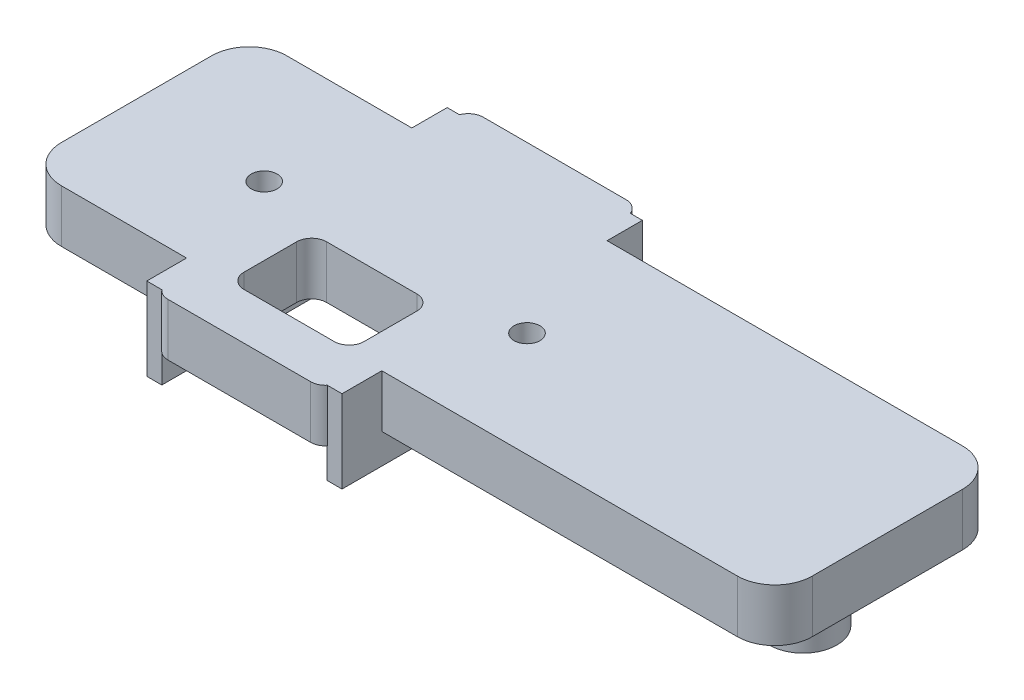
SolidWorks part; units mm, degrees
ref_plane "Front Plane" through (0, 0, 0) normal (0, 0, 1) x (1, 0, 0)
ref_plane "Top Plane" through (0, 0, 0) normal (0, 1, 0) x (1, 0, 0)
ref_plane "Right Plane" through (0, 0, 0) normal (1, 0, 0) x (0, 0, -1)
sketch "Sketch1" plane through (0, 0, 0) normal (0, 1, 0) x (1, 0, 0)
  line L1 (-45.1945, 17.8802) -> (54.8055, 17.8802)
  line L2 (-45.1945, 17.8802) -> (-45.1945, -12.1198)
  line L3 (-45.1945, -12.1198) -> (54.8055, -12.1198)
  line L4 (54.8055, 17.8802) -> (54.8055, -12.1198)
  dimension "D1" = 100
  dimension "D2" = 30
extrude "Boss-Extrude1" add sketch "Sketch1" along normal blind 7
ref_plane "Plane1" through (0, -1, 0) normal (0, -1, 0) x (-1, 0, 0)
sketch "Sketch2" plane through (0, -1, 0) normal (0, -1, 0) x (-1, 0, 0)
  line L0 (-54.8055, 2.8802) -> (57.5711, 2.8802) construction
  line L1 (-41.1646, -0.0198) -> (-44.5646, -0.0198)
  line L2 (-41.1646, -0.0198) -> (-41.1646, 5.7802)
  line L3 (-41.1646, 5.7802) -> (-44.5646, 5.7802)
  line L4 (-44.5646, -0.0198) -> (-44.5646, 5.7802)
  line L5 (-54.8055, -12.1198) -> (-54.8055, 17.8802) construction
  line L6 (-42.8646, -12.1198) -> (-42.8646, 27.765) construction
  line L8 (45.1945, -12.1198) -> (-54.8055, -12.1198) construction
  dimension "D1" = 3.4
  dimension "D2" = 5.8
  dimension "D3" = 1.7
  dimension "D4" = 2.9
extrude "Boss-Extrude2" add sketch "Sketch2" along normal blind 6 separate body
shell "Shell1" thickness 1 removed face at (42.8646, -7, -2.8802) outward yes
sketch "Sketch3" plane through (0, 0, 0) normal (0, -1, 0) x (-1, 0, 0)
  line L0 (-42.8646, -0.0198) -> (-42.8646, 11.0227) construction
  line L1 (-44.5646, -0.0198) -> (-41.1646, -0.0198) construction
  line L2 (-41.1646, 2.8802) -> (-49.8164, 2.8802) construction
  line L3 (-41.1646, -0.0198) -> (-41.1646, 5.7802) construction
  point P9 (-42.8646, 2.8802)
sketch "Sketch4" plane through (0, 0, 0) normal (0, -1, 0) x (-1, 0, 0)
  circle A0 centre (-42.9099, 3.5376) radius 4.5
  circle A1 centre (-42.9099, 3.5376) radius 3.7
extrude "Boss-Extrude3" add sketch "Sketch4" along normal blind 10
sketch "Sketch5" plane through (0, 0, 0) normal (0, -1, 0) x (-1, 0, 0)
  circle A0 centre (-42.8646, 2.8802) radius 4.25
  circle A1 centre (-42.8646, 2.8802) radius 5.5
extrude "Boss-Extrude4" add sketch "Sketch5" along normal blind 4
fillet "Fillet1" radius 5 4 edges at (-45.1945, 3.5, -17.8802) (-45.1945, 3.5, 12.1198) (54.8055, 3.5, -17.8802) (54.8055, 3.5, 12.1198)
sketch "Sketch6" plane through (0, 0, 0) normal (0, -1, 0) x (-1, 0, 0)
  line L0 (40.1945, -12.1198) -> (-49.8055, -12.1198) construction
  line L1 (22.0125, -12.1198) -> (-0.9875, -12.1198)
  line L2 (22.0125, -12.1198) -> (22.0125, -18.1198)
  line L3 (22.0125, -18.1198) -> (-0.9875, -18.1198)
  line L4 (-0.9875, -12.1198) -> (-0.9875, -18.1198)
  line L5 (45.1945, 2.8802) -> (44.2396, 2.8802) construction
  line L6 (45.1945, 12.8802) -> (45.1945, -7.1198) construction
  line L7 (22.0125, 23.8802) -> (-0.9875, 23.8802)
  line L8 (-0.9875, 17.8802) -> (-0.9875, 23.8802)
  line L9 (22.0125, 17.8802) -> (-0.9875, 17.8802)
  line L10 (22.0125, 17.8802) -> (22.0125, 23.8802)
  dimension "D1" = 6
  dimension "D2" = 23
extrude "Boss-Extrude5" add sketch "Sketch6" against normal up to surface (7 mm away) up to face at (4.8055, 7, -2.8802)
sketch "Sketch7" plane through (0, 0, 0) normal (0, -1, 0) x (-1, 0, 0)
  line L0 (40.1945, -12.1198) -> (22.0125, -12.1198) construction
  line L1 (-0.9875, -12.1198) -> (-49.8055, -12.1198) construction
  circle A0 centre (27.1973, 1.8802) radius 1.725
  circle A1 centre (-7.8027, 1.8802) radius 1.725
  dimension "D1" = 35
  dimension "D2" = 14
  dimension "D3" = 14
extrude "Cut-Extrude1" cut sketch "Sketch7" against normal up to surface (7 mm away) up to face at (-2.8535, 7, -2.8802)
fillet "Fillet2" radius 2 4 edges at (0.9875, 3.5, -23.8802) (-22.0125, 3.5, -23.8802) (0.9875, 3.5, 18.1198) (-22.0125, 3.5, 18.1198)
sketch "Sketch8" plane through (0, 0, 0) normal (0, -1, 0) x (-1, 0, 0)
  line L0 (1.0125, -18.1198) -> (20.0125, -18.1198) construction
  line L1 (18.0789, -11.9198) -> (2.0789, -11.9198)
  line L2 (18.0789, -11.9198) -> (18.0789, -0.9198)
  line L3 (18.0789, -0.9198) -> (2.0789, -0.9198)
  line L4 (2.0789, -11.9198) -> (2.0789, -0.9198)
  dimension "D1" = 16
  dimension "D2" = 11
  dimension "D3" = 6.2
extrude "Cut-Extrude2" cut sketch "Sketch8" against normal up to surface (7 mm away) up to face at (-27.1973, 7, -0.1552)
fillet "Fillet3" radius 2 4 edges at (-2.0789, 3.5, 0.9198) (-18.0789, 3.5, 0.9198) (-2.0789, 3.5, 11.9198) (-18.0789, 3.5, 11.9198)
sketch "Sketch9" plane through (0, 0, 0) normal (0, -1, 0) x (-1, 0, 0)
  line L0 (23.5334, 22.5829) -> (23.5334, -17.4171)
  line L1 (21.5334, 22.5829) -> (21.5334, -17.4171)
  line L2 (23.5334, -17.4171) -> (21.5334, -17.4171)
  line L3 (23.5334, 22.5829) -> (21.5334, 22.5829)
  line L6 (-2.4666, 22.5829) -> (-2.4666, -17.4171)
  line L7 (-2.4666, -17.4171) -> (-0.4666, -17.4171)
  line L8 (-0.4666, 22.5829) -> (-0.4666, -17.4171)
  line L9 (-2.4666, 22.5829) -> (-0.4666, 22.5829)
  dimension "D1" = 40
  dimension "D3" = 22
  dimension "D4" = 2
  dimension "D2" = 2
extrude "Boss-Extrude6" add sketch "Sketch9" along normal blind 4 and the other way up to surface (7 mm away) other way up to face at (-10.0789, 7, 6.4198)
